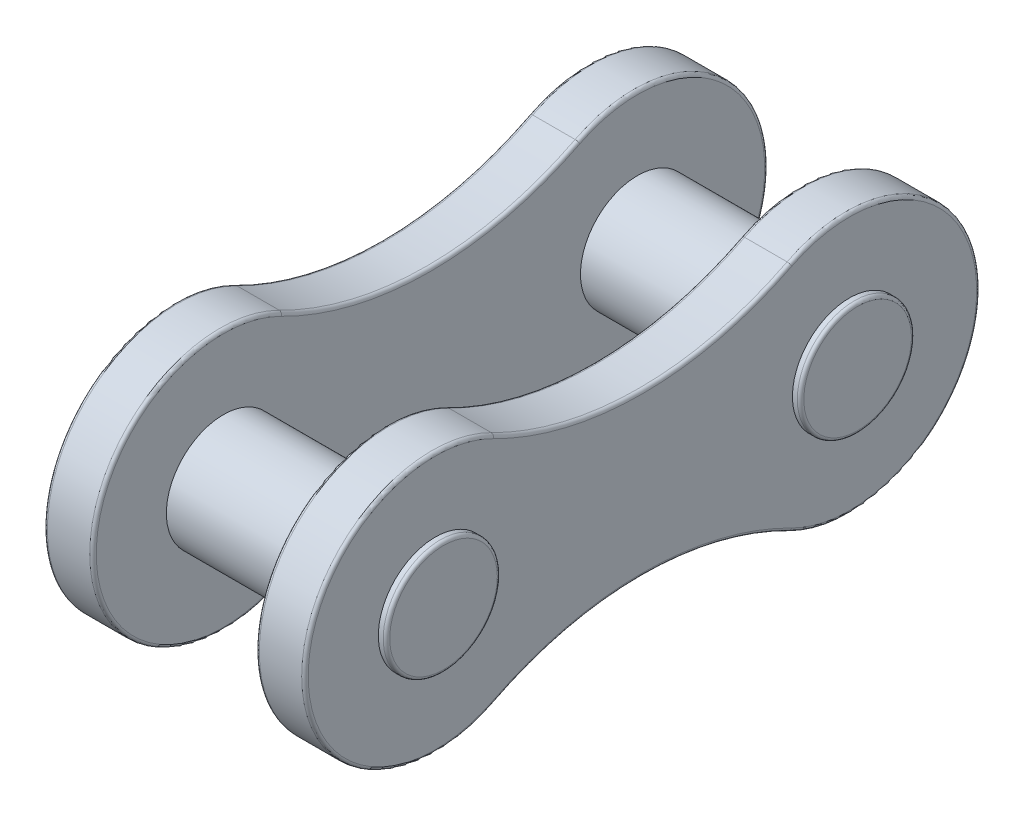
SolidWorks part; units mm, degrees
ref_plane "Front Plane" through (0, 0, 0) normal (0, 0, 1) x (1, 0, 0)
ref_plane "Top Plane" through (0, 0, 0) normal (0, 1, 0) x (1, 0, 0)
ref_plane "Right Plane" through (0, 0, 0) normal (1, 0, 0) x (0, 0, -1)
sketch "Sketch5" plane through (0, 0, 0) normal (1, 0, 0) x (0, 0, -1)
  line L0 (0, -1454.1638) -> (0, 3744.1855) construction
  line L1 (6.35, 0) -> (-6.35, 0) construction
  arc A0 (-4.5357, 3.5649) -> (-4.5357, -3.5649) centre (-6.35, 0) ccw
  circle A1 centre (-6.35, 0) radius 1.75
  circle A2 centre (6.35, 0) radius 1.75
  arc A3 (4.5357, 3.5649) -> (4.5357, -3.5649) centre (6.35, 0) cw
  arc A4 (-4.5357, 3.5649) -> (4.5357, 3.5649) centre (0, 12.4771) ccw
  arc A5 (-4.5357, -3.5649) -> (4.5357, -3.5649) centre (0, -12.4771) cw
  dimension "D1" = 8
  dimension "D2" = 3.5
  dimension "D4" = 10
  dimension "D3" = 12.7
extrude "Boss-Extrude2" add sketch "Sketch5" along normal blind 1.5 from offset 2.5
sketch "Sketch6" plane through (0, 0, 0) normal (1, 0, 0) x (0, 0, -1)
  circle A0 centre (6.35, 0) radius 1.75 construction
  circle A1 centre (-6.35, 0) radius 1.75 construction
  circle A2 centre (6.35, 0) radius 1.75
  circle A3 centre (-6.35, 0) radius 1.75
  arc A4 (-4.5357, 3.5649) -> (4.5357, 3.5649) centre (0, 12.4771) ccw
  arc A5 (-4.5357, 3.5649) -> (-4.5357, -3.5649) centre (-6.35, 0) ccw
  arc A6 (4.5357, -3.5649) -> (-4.5357, -3.5649) centre (0, -12.4771) ccw
  arc A7 (4.5357, -3.5649) -> (4.5357, 3.5649) centre (6.35, 0) ccw
  arc A8 (-4.5357, 3.5649) -> (4.5357, 3.5649) centre (0, 12.4771) ccw
  arc A9 (-4.5357, 3.5649) -> (-4.5357, -3.5649) centre (-6.35, 0) ccw
  arc A10 (4.5357, -3.5649) -> (-4.5357, -3.5649) centre (0, -12.4771) ccw
  arc A11 (4.5357, -3.5649) -> (4.5357, 3.5649) centre (6.35, 0) ccw
  dimension "D1" = 0
extrude "Boss-Extrude3" add sketch "Sketch6" against normal blind 1.5 from offset 2.5 separate body offset against normal yes
sketch "Sketch7" plane through (0, 0, 0) normal (1, 0, 0) x (0, 0, -1)
  circle A0 centre (6.35, 0) radius 1.75 construction
  circle A1 centre (-6.35, 0) radius 1.75 construction
  circle A2 centre (6.35, 0) radius 1.75
  circle A3 centre (-6.35, 0) radius 1.75
extrude "Boss-Extrude4" add sketch "Sketch7" along normal mid plane 8.5
fillet "Fillet1" radius 0.1 20 edges at (4, 0, -10.35) (4, -2.4771, 0) (4, 0, 10.35) (2.5, 0, -10.35) (2.5, -2.4771, 0) (2.5, 0, 10.35) (-4, 0, -10.35) (-4, -2.4771, 0) (-4, 0, 10.35) (-2.5, 0, -10.35) (-2.5, -2.4771, 0) (-2.5, 0, 10.35) (4, 2.4771, 0) (2.5, 2.4771, 0) (-4, 2.4771, 0) (-2.5, 2.4771, 0) (-4.25, 0, -8.1) (-4.25, 0, 4.6) (4.25, 0, -8.1) (4.25, 0, 4.6)
